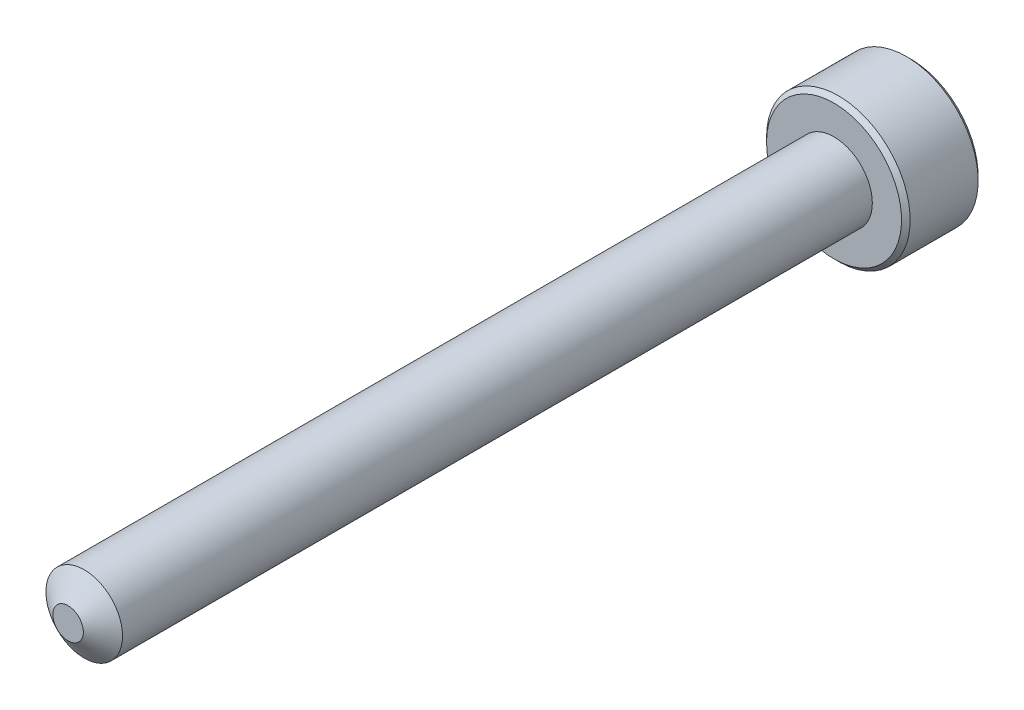
SolidWorks part; units mm, degrees
ref_plane "Front Plane" through (0, 0, 0) normal (0, 0, 1) x (1, 0, 0)
ref_plane "Top Plane" through (0, 0, 0) normal (0, 1, 0) x (1, 0, 0)
ref_plane "Right Plane" through (0, 0, 0) normal (1, 0, 0) x (0, 0, -1)
sketch "Sketch1" plane through (0, 0, 0) normal (0, 0, 1) x (1, 0, 0)
  circle A0 centre (0, 0) radius 0.8
  dimension "OD" = 1.6
extrude "Extrude1" add sketch "Sketch1" against normal blind 16
sketch "Sketch2" plane through (0, 0, 0) normal (0, 0, 1) x (1, 0, 0)
  circle A0 centre (0, 0) radius 0.8 construction
  circle A1 centre (0, 0) radius 0.8
curve "Helix/Spiral1" [suppressed] pitch 0.35 height 16.35 turns 46.7143 parameters "pitch"=0.35
sketch "Sketch3" plane through (0, 0, 0) normal (1, 0, 0) x (0, 0, -1)
  line L0 (-0.3063, 0.8) -> (-0.175, 0.5727)
  line L1 (-0.175, 0.5727) -> (-0.1313, 0.5727)
  line L2 (-0.1313, 0.5727) -> (0, 0.8)
  line L3 (-0.3063, 0.8) -> (0, 0.8)
  line L4 (-0.1531, 0.8) -> (-0.1531, 0.5727) construction
  line L5 (-0.2406, 0.6863) -> (-0.0656, 0.6863) construction
  line L6 (0, 0.8) -> (0, -0.8) construction
  line L7 (0, -0.8) -> (16, -0.8) construction
  point P11 (1.575, -0.8)
  dimension "D1" = 0.0437
  dimension "D2" = 0.175
  dimension "D3" = 60
  dimension "D4" = 1.575
sweep "Cut-Sweep1" [suppressed] cut profiles "Sketch3" path "Helix/Spiral1"
sketch "Sketch4" plane through (0, 0, 0) normal (1, 0, 0) x (0, 0, -1)
  line L0 (0.337, 0.8) -> (0, 0.3187)
  line L1 (0, 0.3187) -> (0, 0.8)
  line L2 (0.337, 0.8) -> (0, 0.8)
  line L3 (-0.3063, 0.8) -> (0, 0.8) construction
  line L4 (0, 0) -> (7.0209, 0) construction
  dimension "D1" = 55
  dimension "D2" = 0.254
revolve "Cut-Revolve1" cut sketch "Sketch4" angle 360 about L4
sketch "Sketch5" [suppressed] plane through (0, 0, 0) normal (1, 0, 0) x (0, 0, -1)
  line L0 (16, -0.7513) -> (16, 0.1227) construction
  line L1 (16, 0.8) -> (84.1202, 0.8)
  line L2 (16, 0.8) -> (16, 0)
  line L3 (16, 0) -> (84, 0)
  line L4 (84, 0.4698) -> (84, 0)
  line L5 (84.1202, 0.8) -> (84, 0.4698)
  line L6 (0, 0) -> (9.9695, 0) construction
  point P3 (84, 0.8)
  point P10 (84, 0.8)
  dimension "D1" = 0.3302
  dimension "Thread min" = 84
  dimension "D3" = 20
revolve "partially thread" [suppressed] add sketch "Sketch5" angle 360 about L6
sketch "Sketch6" plane through (0, 0, -16) normal (0, 0, -1) x (-1, 0, 0)
  circle A0 centre (0, 0) radius 1.5
  dimension "head dia" = 3
extrude "Extrude2" add sketch "Sketch6" along normal blind 1.6
sketch "Sketch7" plane through (0, 0, -17.6) normal (0, 0, -1) x (-1, 0, 0)
  line L1 (0, 0.866) -> (-0.75, 0.433)
  line L2 (-0.75, 0.433) -> (-0.75, -0.433)
  line L3 (-0.75, -0.433) -> (0, -0.866)
  line L4 (0, -0.866) -> (0.75, -0.433)
  line L5 (0.75, -0.433) -> (0.75, 0.433)
  line L6 (0.75, 0.433) -> (0, 0.866)
  circle A0 centre (0, 0) radius 0.75 construction
  dimension "hex dia" = 1.5
extrude "Cut-Extrude1" cut sketch "Sketch7" against normal blind 1.125
sketch "Sketch8" plane through (0, 0, -17.6) normal (0, 0, -1) x (-1, 0, 0)
  circle A0 centre (0, 0) radius 0.866
extrude "Cut-Extrude2" cut sketch "Sketch8" against normal through all draft 45
chamfer "Chamfer1" distance 0.09 angle 45 2 edges at (-1.5, 0, -17.6) (-1.5, 0, -16)
sketch "Sketch9" plane through (0, 0, 0) normal (1, 0, 0) x (0, 0, -1)
  line L0 (0, 0.8) -> (0, -0.8) construction
  line L1 (1.925, 0.8) -> (1.925, -0.8) construction
  dimension "D1" = 1.925
sketch "Sketch10" plane through (0, 0, 0) normal (1, 0, 0) x (0, 0, -1)
  line L0 (16, 0.8) -> (16, 0)
  line L1 (16, 0.8) -> (15.9125, 0.8)
  line L2 (15.9125, 0.8) -> (15.5811, 0)
  line L3 (16, 0) -> (15.5811, 0)
  line L4 (16, 1.41) -> (16, -1.41) construction
  dimension "D1" = 22.5
  dimension "D2" = 0.0875
revolve "Revolve1" add sketch "Sketch10" angle 360 about L3
equation "\"D3@Helix/Spiral1\" = \"screw length@Extrude1\"+\"pitch@Helix/Spiral1\""
equation "\"D1@Sketch3\" = \"pitch@Helix/Spiral1\"*.125"
equation "\"D2@Sketch3\" = \"pitch@Helix/Spiral1\"*.5"
equation "\"D1@Cut-Extrude1\" = \"hex dia@Sketch7\"*.75"
equation "\"D1@Chamfer1\" = \"head dia@Sketch6\"*.03"
equation "\"D1@Sketch9\" = \"pitch@Helix/Spiral1\"*5.5"
equation "\"D2@Sketch10\" = \"pitch@Helix/Spiral1\"*.25"
equation "\"D4@Sketch3\" = \"pitch@Helix/Spiral1\"*4.50"
